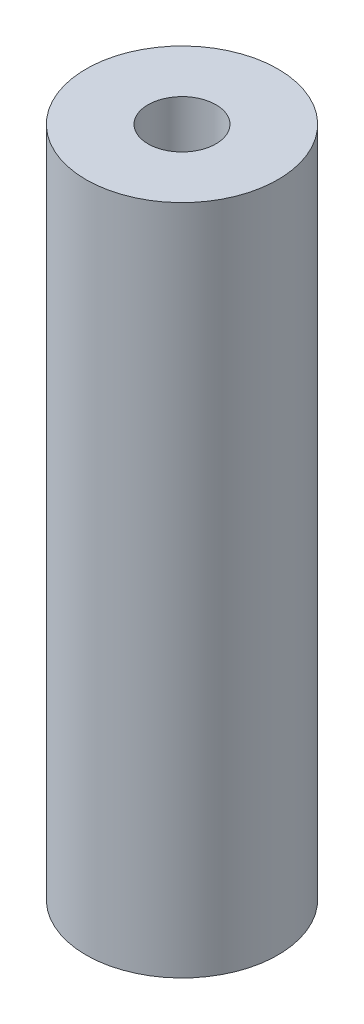
SolidWorks part; units mm, degrees
ref_plane "Front Plane" through (0, 0, 0) normal (0, 0, 1) x (1, 0, 0)
ref_plane "Top Plane" through (0, 0, 0) normal (0, 1, 0) x (1, 0, 0)
ref_plane "Right Plane" through (0, 0, 0) normal (1, 0, 0) x (0, 0, -1)
sketch "Sketch1" plane through (0, 0, 0) normal (0, 1, 0) x (1, 0, 0)
  circle A0 centre (0, 0) radius 6.35
  dimension "D1" = 12.7
extrude "Boss-Extrude1" add sketch "Sketch1" along normal blind 44.45
hole_wizard "#8 Clearance Hole1" positions "Sketch2" profile "Sketch3" hole size "#8" standard "ANSI Inch" end condition through all
sketch "Sketch2" plane through (0, 44.45, 0) normal (0, 1, 0) x (1, 0, 0)
  point P0 (0, 0)
sketch "Sketch3" plane through (0, 44.45, 0) normal (1, 0, 0) x (0, 0, 1)
  line L0 (0, 0) -> (0, 44.45)
  line L1 (0, 44.45) -> (2.2479, 44.45)
  line L2 (2.2479, 44.45) -> (2.2479, 0)
  line L5 (2.2479, 0) -> (0, 0)
  line L11 (0, -6.35) -> (0, 107.95) construction
  dimension "Thru Hole Dia." = 4.4958
  dimension "Thru Hole Depth" = 44.45
